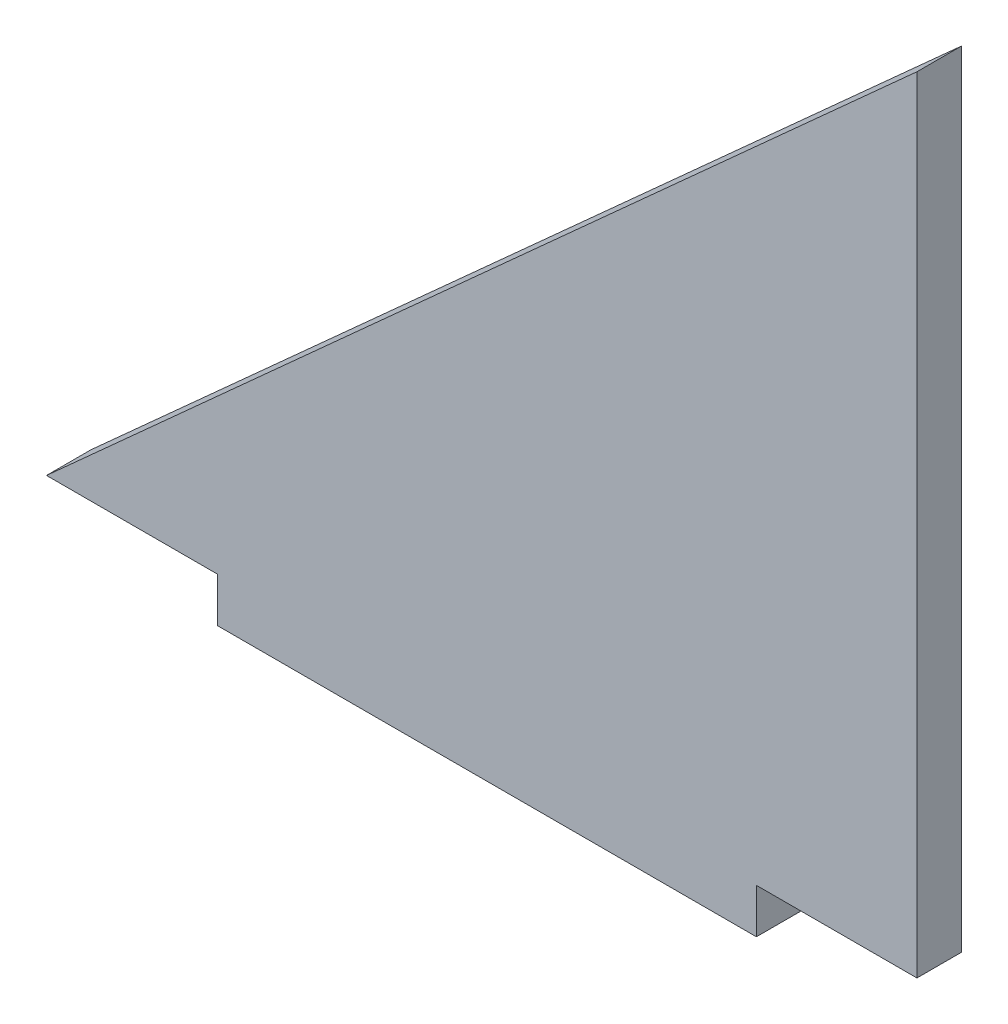
SolidWorks part; units mm, degrees
ref_plane "Front Plane" through (0, 0, 0) normal (0, 0, 1) x (1, 0, 0)
ref_plane "Top Plane" through (0, 0, 0) normal (0, 1, 0) x (1, 0, 0)
ref_plane "Right Plane" through (0, 0, 0) normal (1, 0, 0) x (0, 0, -1)
sketch "Sketch1" plane through (0, 0, 0) normal (0, 0, 1) x (1, 0, 0)
  line L0 (-61.976, 0) -> (-49.784, 0) construction
  line L1 (-61.976, 0) -> (0, 55.88)
  line L2 (0, 55.88) -> (0, 0)
  line L3 (0, 0) -> (-11.43, 0)
  line L5 (-49.784, 0) -> (-49.784, -3.175)
  line L6 (-49.784, -3.175) -> (-11.43, -3.175)
  line L7 (-11.43, 0) -> (-11.43, -3.175)
  line L8 (-49.784, 0) -> (-61.976, 0)
  line L9 (-11.43, 0) -> (0, 0) construction
  dimension "D1" = 3.175
  dimension "D2" = 38.354
  dimension "D3" = 11.43
  dimension "D4" = 55.88
  dimension "D5" = 12.192
extrude "Boss-Extrude1" add sketch "Sketch1" along normal blind 3.175
